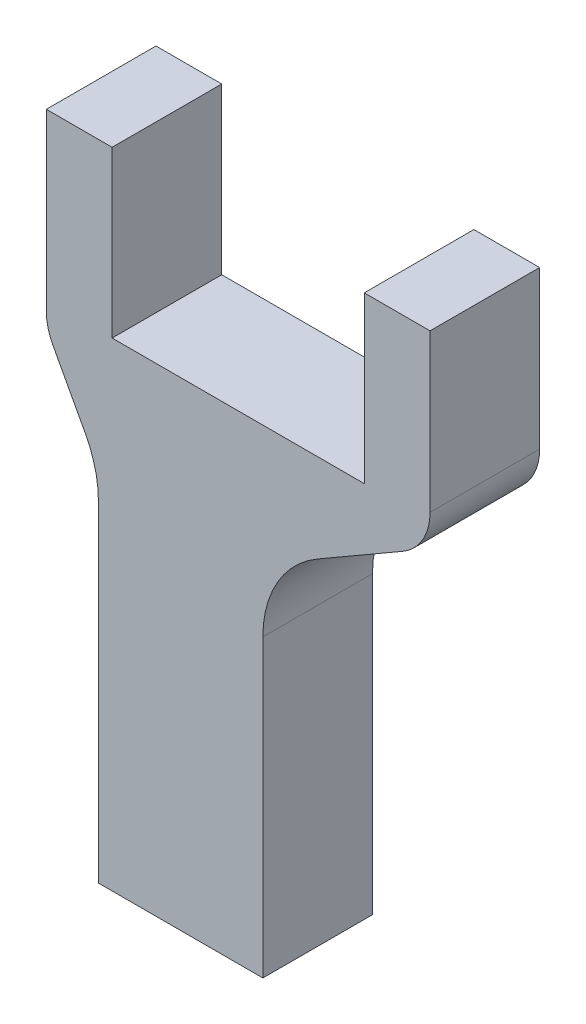
SolidWorks part; units mm, degrees
ref_plane "Front Plane" through (0, 0, 0) normal (0, 0, 1) x (1, 0, 0)
ref_plane "Top Plane" through (0, 0, 0) normal (0, 1, 0) x (1, 0, 0)
ref_plane "Right Plane" through (0, 0, 0) normal (1, 0, 0) x (0, 0, -1)
sketch "Sketch1" plane through (0, 0, 0) normal (0, 0, 1) x (1, 0, 0)
  line L0 (-7.5, 465.3207) -> (-7.5, 488.0002) construction
  line L2 (-7.5, 467.3207) -> (-7.5, 500.038)
  line L3 (-6.25, 511.0002) -> (16.75, 511.0002)
  line L4 (7.5, 467.3207) -> (7.5, 500.038)
  line L5 (7.5, 488.0002) -> (7.5, 465.3207) construction
  line L6 (5.5, 467.3207) -> (-5.5, 467.3207) construction
  line L7 (7.5, 467.3207) -> (-7.5, 467.3207)
  line L9 (-6.25, 526.0712) -> (-6.25, 511.0002)
  line L11 (16.75, 526.0712) -> (16.75, 511.0002)
  line L12 (16.5, 512.5012) -> (16.5, 524.8512) construction
  line L13 (-6, 512.5012) -> (-6, 524.8512) construction
  line L15 (22.75, 526.0712) -> (22.75, 508.8426)
  line L16 (22.75, 508.8426) -> (7.5, 500.038)
  line L17 (16.75, 526.0712) -> (22.75, 526.0712)
  line L18 (-6.25, 526.0712) -> (-12.25, 526.0712)
  line L19 (-12.25, 526.0712) -> (-12.25, 508.8426)
  line L20 (-12.25, 508.8426) -> (-7.5, 500.038)
  circle A0 centre (0, 491.0002) radius 1 construction
  point P1 (-11.6267, 508.8426)
  dimension "D1" = 0
  dimension "D2" = 20
  dimension "D3" = 0.25
  dimension "D4" = 0.25
  dimension "D5" = 6
  dimension "D6" = 6
extrude "Boss-Extrude1" add sketch "Sketch1" along normal blind 10
fillet "Fillet1" radius 10 2 edges at (-7.5, 500.038, 5) (7.5, 500.038, 5)
fillet "Fillet2" radius 5 2 edges at (-12.25, 508.8426, 5) (22.75, 508.8426, 5)
